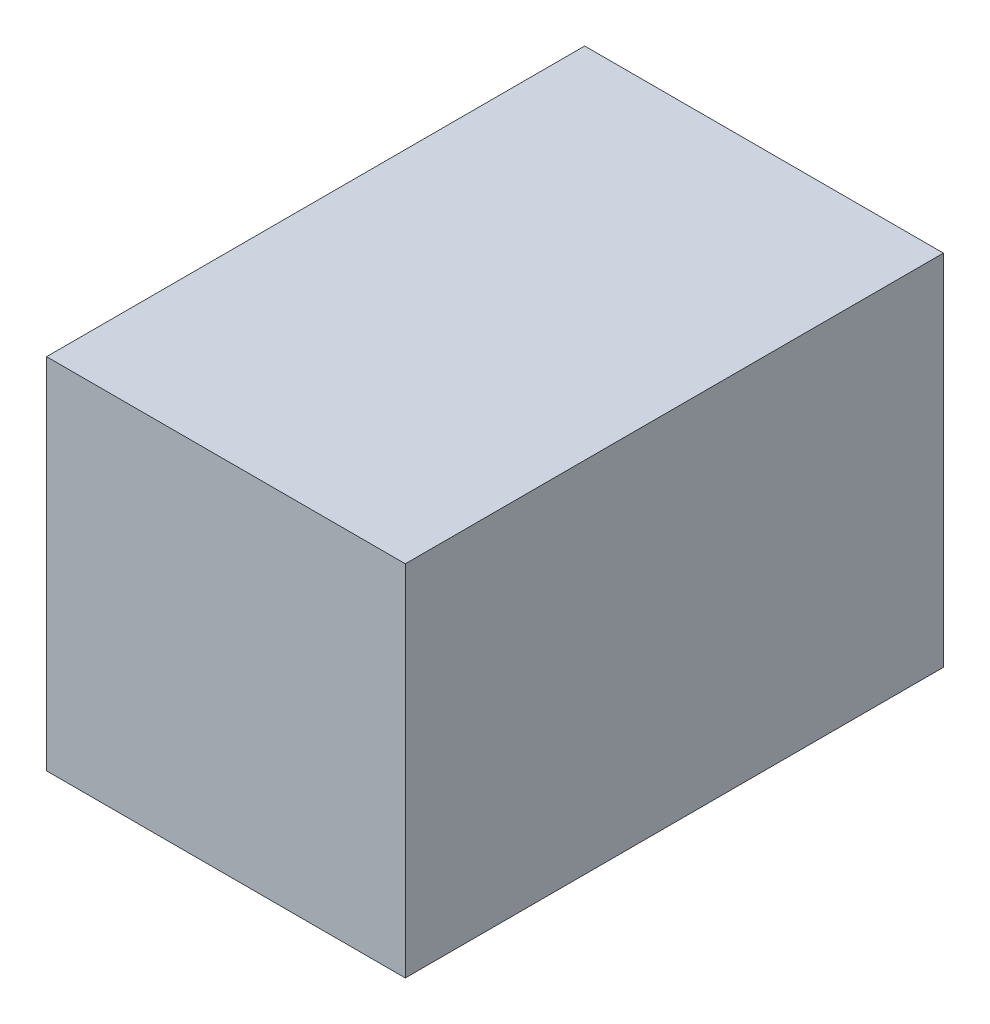
SolidWorks part; units mm, degrees
ref_plane "Front Plane" through (0, 0, 0) normal (0, 0, 1) x (1, 0, 0)
ref_plane "Top Plane" through (0, 0, 0) normal (0, 1, 0) x (1, 0, 0)
ref_plane "Right Plane" through (0, 0, 0) normal (1, 0, 0) x (0, 0, -1)
sketch "Sketch1" plane through (0, 0, 0) normal (0, 0, 1) x (1, 0, 0)
  line L7 (0, 0) -> (-20, 0)
  line L8 (0, 0) -> (0, 20)
  line L9 (0, 20) -> (-20, 20)
  line L10 (-20, 0) -> (-20, 20)
  dimension "D1" = 20
  dimension "D2" = 20
extrude "Boss-Extrude1" add sketch "Sketch1" along normal blind 30
equation "\"height\"=20"
equation "\"width\"=20"
equation "\"D1@Sketch1\"=\"width\""
equation "\"D2@Sketch1\"=\"height\""
equation "\"length\"=30"
equation "\"D1@Boss-Extrude1\"=\"length\""
